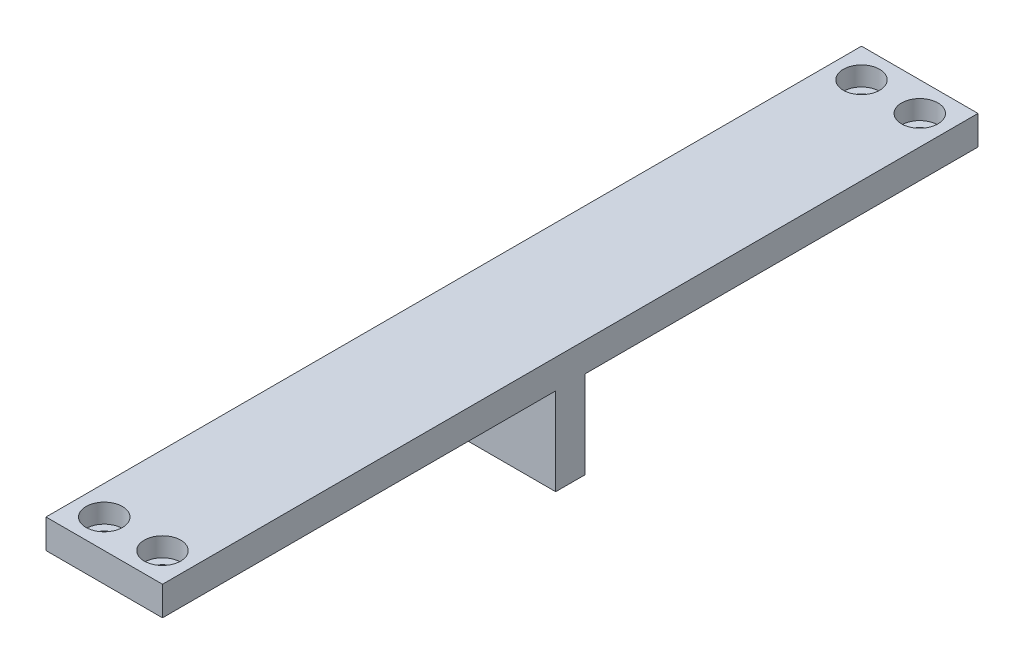
SolidWorks part; units mm, degrees
material "6061 Alloy"
ref_plane "Front Plane" through (0, 0, 0) normal (0, 0, 1) x (1, 0, 0)
ref_plane "Top Plane" through (0, 0, 0) normal (0, 1, 0) x (1, 0, 0)
ref_plane "Right Plane" through (0, 0, 0) normal (1, 0, 0) x (0, 0, -1)
sketch "Sketch1" plane through (0, 0, 0) normal (0, 1, 0) x (1, 0, 0)
  line L1 (-12.7, -88.9) -> (12.7, -88.9)
  line L2 (-12.7, -88.9) -> (-12.7, 88.9)
  line L3 (-12.7, 88.9) -> (12.7, 88.9)
  line L4 (12.7, -88.9) -> (12.7, 88.9)
  line L5 (-12.7, -88.9) -> (12.7, 88.9) construction
  line L6 (-12.7, 88.9) -> (12.7, -88.9) construction
  point P0 (0, 0)
  dimension "D1" = 177.8
  dimension "D2" = 25.4
extrude "Boss-Extrude1" add sketch "Sketch1" along normal blind 6.35
sketch "Sketch2" plane through (0, 0, 0) normal (0, -1, 0) x (-1, 0, 0)
  line L0 (-12.7, -88.9) -> (-12.7, 88.9) construction
  line L1 (12.7, 3.175) -> (-12.7, 3.175)
  line L2 (12.7, 3.175) -> (12.7, -3.175)
  line L3 (12.7, -3.175) -> (-12.7, -3.175)
  line L4 (-12.7, 3.175) -> (-12.7, -3.175)
  line L5 (12.7, 3.175) -> (-12.7, -3.175) construction
  line L6 (12.7, -3.175) -> (-12.7, 3.175) construction
  point P0 (0, 0)
  dimension "D1" = 6.35
extrude "Boss-Extrude2" add sketch "Sketch2" along normal blind 19.05
sketch "Sketch3" plane through (0, -19.05, 0) normal (0, -1, 0) x (-1, 0, 0)
  line L1 (1.5875, 1.5875) -> (-1.5875, 1.5875)
  line L2 (1.5875, 1.5875) -> (1.5875, -1.5875)
  line L3 (1.5875, -1.5875) -> (-1.5875, -1.5875)
  line L4 (-1.5875, 1.5875) -> (-1.5875, -1.5875)
  line L5 (1.5875, 1.5875) -> (-1.5875, -1.5875) construction
  line L6 (1.5875, -1.5875) -> (-1.5875, 1.5875) construction
  circle A0 centre (1.5875, -1.5875) radius 0.381
  circle A1 centre (-1.5875, -1.5875) radius 0.381
  circle A2 centre (-1.5875, 1.5875) radius 0.381
  circle A3 centre (1.5875, 1.5875) radius 0.381
  point P0 (0, 0)
  dimension "D3" = 0.762
  dimension "D4" = 0.762
  dimension "D5" = 0.762
  dimension "D1" = 3.175
  dimension "D2" = 3.175
extrude "Cut-Extrude1" cut sketch "Sketch3" against normal blind 1.5875 contours A3 L1 A2 L4 A1 L3 A0 L2 | L3 A0 L2 | L2 A0 L3 | L1 A3 L2 | L2 A3 L1 | L1 A2 L4 | L4 A2 L1 | L3 A1 L4 | L4 A1 L3 region at (1.4258, -19.05, -1.4258) region at (1.6414, -19.05, -1.6414) region at (0, -19.05, 0) region at (-1.6414, -19.05, -1.6414) region at (-1.4258, -19.05, -1.4258) region at (1.4258, -19.05, 1.4258) region at (1.6414, -19.05, 1.6414) region at (-1.6414, -19.05, 1.6414) region at (-1.4258, -19.05, 1.4258)
hole_wizard "CBORE for #8 Socket Head Cap Screw1" positions "Sketch4" profile "Sketch5" counterbore size "#8" standard "ANSI Inch" end condition up to next
sketch "Sketch4" plane through (0, 6.35, 0) normal (0, 1, 0) x (1, 0, 0)
  line L0 (-12.7, 88.9) -> (-12.7, -88.9) construction
  line L1 (-12.7, -88.9) -> (12.7, -88.9) construction
  line L2 (12.7, 88.9) -> (-12.7, 88.9) construction
  point P0 (-6.35, -82.55)
  point P2 (6.35, -82.55)
  point P4 (6.35, 82.55)
  point P6 (-6.35, 82.55)
  dimension "D1" = 6.35
  dimension "D2" = 6.35
  dimension "D3" = 6.35
  dimension "D4" = 19.05
  dimension "D5" = 6.35
  dimension "D6" = 19.05
  dimension "D7" = 6.35
  dimension "D8" = 6.35
sketch "Sketch5" plane through (-6.35, 6.35, 82.55) normal (1, 0, 0) x (0, 0, 1)
  line L0 (0, 0) -> (0, 6.35)
  line L1 (0, 6.35) -> (2.1526, 6.35)
  line L3 (2.1526, 6.35) -> (2.1527, 4.1656)
  line L4 (2.1527, 4.1656) -> (3.9687, 4.1656)
  line L5 (3.9687, 4.1656) -> (3.9687, 0)
  line L7 (3.9687, 0) -> (0, 0)
  line L11 (0, -6.35) -> (0, 107.95) construction
  dimension "Thru Hole Dia." = 4.3053
  dimension "Thru Hole Depth" = 6.35
  dimension "C'Bore Dia." = 7.9375
  dimension "C'Bore Depth" = 4.1656
